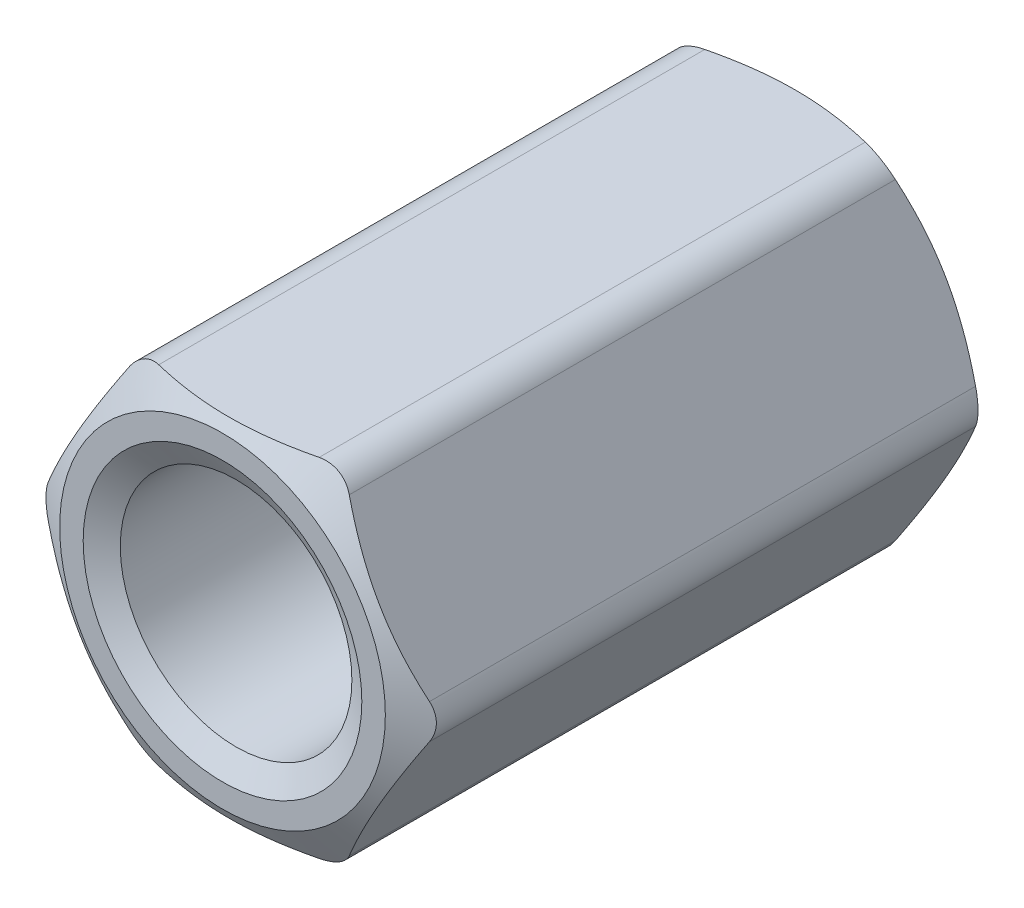
SolidWorks part; units mm, degrees
ref_plane "Front Plane" through (0, 0, 0) normal (0, 0, 1) x (1, 0, 0)
ref_plane "Top Plane" through (0, 0, 0) normal (0, 1, 0) x (1, 0, 0)
ref_plane "Right Plane" through (0, 0, 0) normal (1, 0, 0) x (0, 0, -1)
sketch "Sketch1" plane through (0, 0, 0) normal (0, 0, 1) x (1, 0, 0)
  line L1 (1.7321, -3) -> (3.4641, 0)
  line L2 (3.4641, 0) -> (1.7321, 3)
  line L3 (1.7321, 3) -> (-1.7321, 3)
  line L4 (-1.7321, 3) -> (-3.4641, 0)
  line L5 (-3.4641, 0) -> (-1.7321, -3)
  line L6 (-1.7321, -3) -> (1.7321, -3)
  circle A0 centre (0, 0) radius 3 construction
  point P10 (0, -3)
  dimension "Hex Size" = 6
sketch "Sketch2" plane through (0, 0, 0) normal (1, 0, 0) x (0, 0, -1)
  line L0 (5, 0) -> (-5, 0) construction
  line L3 (5, 2) -> (5, -2) construction
  line L4 (-5.6563, 2.0758) -> (-5.3063, 1.4696) construction
  line L5 (-5.3063, 1.4696) -> (-4.9563, 2.0758) construction
  line L6 (-4.9563, 2.0758) -> (-5.6563, 2.0758) construction
  line L7 (-5.6125, 2) -> (-5, 2) construction
  line L8 (-5.35, 1.5453) -> (-5.2625, 1.5453) construction
  line L9 (-5.3063, 1.5453) -> (-5.3063, 1.4696) construction
  line L10 (-5.3063, 2) -> (-5.3063, 2.0758) construction
  line L11 (5, 3) -> (-5, 3) construction
  point P6 (0, 3)
  point P9 (5, 0)
  dimension "Thread Length" = 10
  dimension "Thread Size" = 4
  dimension "Thread Pitch" = 0.7
  dimension "Thread Pitch (B)/8" = 0.0875
  dimension "Length" = 10
sketch "Sketch3" plane through (0, 0, 0) normal (1, 0, 0) x (0, 0, -1)
  line L2 (5, 3) -> (5, 2.4062)
  line L3 (5, 2.4062) -> (4.7655, 2)
  line L6 (5, 3) -> (5, 2.4062)
  line L8 (4.7655, 2) -> (-4.7655, 2)
  line L9 (-4.7655, 2) -> (-5, 2.4062)
  line L10 (0, 3) -> (5, 3)
  line L11 (-5, 2.4062) -> (-5, 3)
  line L12 (-5, 3) -> (0, 3)
  line L13 (-5, 2.8125) -> (-5, -2.8125) construction
  line L15 (-4.7655, 2) -> (-4.7655, 2.2708) construction
  line L16 (-4.7655, 2.2708) -> (-4.7655, 2.5417) construction
  line L17 (-4.7655, 2.5417) -> (-4.7655, 2.8125) construction
  line L18 (-4.8033, 2.0656) -> (-4.7655, 2) construction
  line L19 (-5.3063, 2) -> (-5.3063, 2.0758) construction
  point P5 (-5, -3)
  point P15 (-4.7655, 2.4062)
  point P20 (-4.8033, 2.0656)
  dimension "D1" = 60
  dimension "D3" = 5.625
revolve "Revolve1" add sketch "Sketch3" angle 360 about L0
sketch "Sketch4" plane through (0, 0, 0) normal (0, 0, 1) x (1, 0, 0)
  line L0 (0, 3) -> (0, 2) construction
  line L1 (-1.7321, 3) -> (-3.4641, 0)
  line L2 (-3.4641, 0) -> (-1.7321, -3)
  line L3 (-1.7321, -3) -> (1.7321, -3)
  line L4 (1.7321, -3) -> (3.4641, 0)
  line L5 (3.4641, 0) -> (1.7321, 3)
  line L6 (1.7321, 3) -> (-1.7321, 3)
  line L7 (1.7321, -3) -> (3.4641, 0) construction
  circle A0 centre (0, 0) radius 3 construction
  circle A1 centre (0, 0) radius 2.5
  circle A2 centre (0, 0) radius 3 construction
  point P16 (0, 2.5)
extrude "Boss-Extrude1" add sketch "Sketch4" against normal mid plane 10
sketch "Sketch5" plane through (0, 0, 5) normal (0, 0, 1) x (1, 0, 0)
  line L0 (0, 2) -> (0, -2) construction
  line L1 (0, 2) -> (0, -2) construction
  circle A0 centre (0, 0) radius 2.8125
  point P11 (0, -2)
extrude "Cut-Extrude1" cut sketch "Sketch5" against normal through all draft 60 flip side to cut
sketch "Sketch6" plane through (0, 0, -5) normal (0, 0, -1) x (-1, 0, 0)
  circle A0 centre (0, 0) radius 2.8125
  circle A1 centre (0, 0) radius 2.8125 construction
extrude "Cut-Extrude2" cut sketch "Sketch6" against normal through all draft 60 flip side to cut
fillet "Fillet1" radius 0.6 6 edges at (1.7321, 3, 0) (-3.4641, 0, 0) (-1.7321, -3, 0) (1.7321, -3, 0) (3.4641, 0, 0) (-1.7321, 3, 0)
sketch "Drawing 1" plane through (0, 0, 0) normal (1, 0, 0) x (0, 0, -1)
  line L0 (5, -2) -> (-5, -2) construction
  line L1 (5, 2) -> (-5, 2) construction
  line L3 (5, 0) -> (-5, 0) construction
sketch "Sketch7" [suppressed] plane through (0, 0, -5) normal (0, 0, -1) x (-1, 0, 0)
  circle A0 centre (0, 0) radius 2.4062
extrude "Boss-Extrude2" [suppressed] add sketch "Sketch7" along normal up to surface (10 mm away)
sketch "Sketch8" [suppressed] plane through (0, 0, 0) normal (1, 0, 0) x (0, 0, -1)
  line L0 (5, 0) -> (-5, 0) construction
  line L1 (5, 2) -> (-5, 2)
  line L2 (5, 2) -> (5, 0)
  line L3 (5, 0) -> (-5, 0)
  line L4 (-5, 2) -> (-5, 0)
revolve "Revolve2" [suppressed] add sketch "Sketch8" angle 360 about L0
sketch "Sketch9" [suppressed] plane through (0, 0, 5) normal (0, 0, 1) x (1, 0, 0)
  circle A0 centre (0, 0) radius 2
  circle A1 centre (0, 0) radius 2 construction
sketch "Sketch10" [suppressed] plane through (0, 0, 0) normal (1, 0, 0) x (0, 0, -1)
  line L0 (-5.35, 1.5453) -> (-5.2625, 1.5453)
  line L1 (-5.2625, 1.5453) -> (-4.9781, 2.0379)
  line L2 (-5.3063, 1.4696) -> (-4.9563, 2.0758) construction
  line L3 (-4.9781, 2.0379) -> (-5.6344, 2.0379)
  line L4 (-5.6563, 2.0758) -> (-5.3063, 1.4696) construction
  line L5 (-5.6344, 2.0379) -> (-5.35, 1.5453)
  line L6 (-5.3063, 2) -> (-5.3063, 2.0758) construction
  point P12 (-5.3063, 2.0379)
curve "Helix/Spiral1" [suppressed] pitch 0.7 height 8.4 turns 12
sweep "Cut-Sweep1" [suppressed] cut profiles "Sketch10" path "Helix/Spiral1"
pattern_linear "LPattern1" [suppressed] count 2 spacing 7 of bodies 114
combine bodies "Combine1" [suppressed] operation type subtract main body 113 bodies to subtract 119
ref_plane "Plane1" [suppressed] through (0, 0, 4.8033) normal (0, 0, 1) x (1, 0, 0)
sketch "Sketch11" [suppressed] plane through (0, 0, 5) normal (0, 0, 1) x (1, 0, 0)
  circle A0 centre (0, 0) radius 2.4062
extrude "Cut-Extrude3" [suppressed] cut sketch "Sketch11" against normal through all draft 60
sketch "Sketch12" [suppressed] plane through (0, 0, 4.8033) normal (0, 0, 1) x (1, 0, 0)
  circle A0 centre (0, 0) radius 2.0508
  circle A1 centre (0, 0) radius 2 construction
  dimension "D1" = 0.0508
extrude "Cut-Extrude4" [suppressed] cut sketch "Sketch12" against normal through all draft 45
mirror "Mirror1" [suppressed] about plane through (0, 0, 0) normal (0, 0, 1)
equation "\"Thread Pitch (B)/8@Sketch2\" = \"Thread Pitch@Sketch2\" / 8"
equation "\"D1@Fillet1\" = \"Hex Size@Sketch1\" * .1"
equation "\"D3@Helix/Spiral1\" = \"segment length\" + \"Thread Pitch@Sketch2\""
equation "\"D4@Helix/Spiral1\" = \"Thread Pitch@Sketch2\""
equation "\"Thread Length@Sketch2\"=\"Length@Sketch2\""
equation "\"D1@Boss-Extrude1\" = \"Length@Sketch2\""
equation "\"thread count\"= \"Length@Sketch2\" * .75 / \"Thread Pitch@Sketch2\""
equation "\"rounded thread count\"= IIF ( \"thread count\" - int ( \"thread count\" ) > 0 , int ( \"thread count\" ) + 1 , \"thread count\" )"
equation "\"segment length\"= \"Thread Pitch@Sketch2\" * \"rounded thread count\""
equation "\"D3@LPattern1\"=\"segment length\"-\"thread pitch@sketch2\""
equation "\"D3@Cut-Extrude3\"=\"D1@Sketch3\""
equation "\"D3@Sketch3\"=\"Hex Size@Sketch1\"*.9375"
